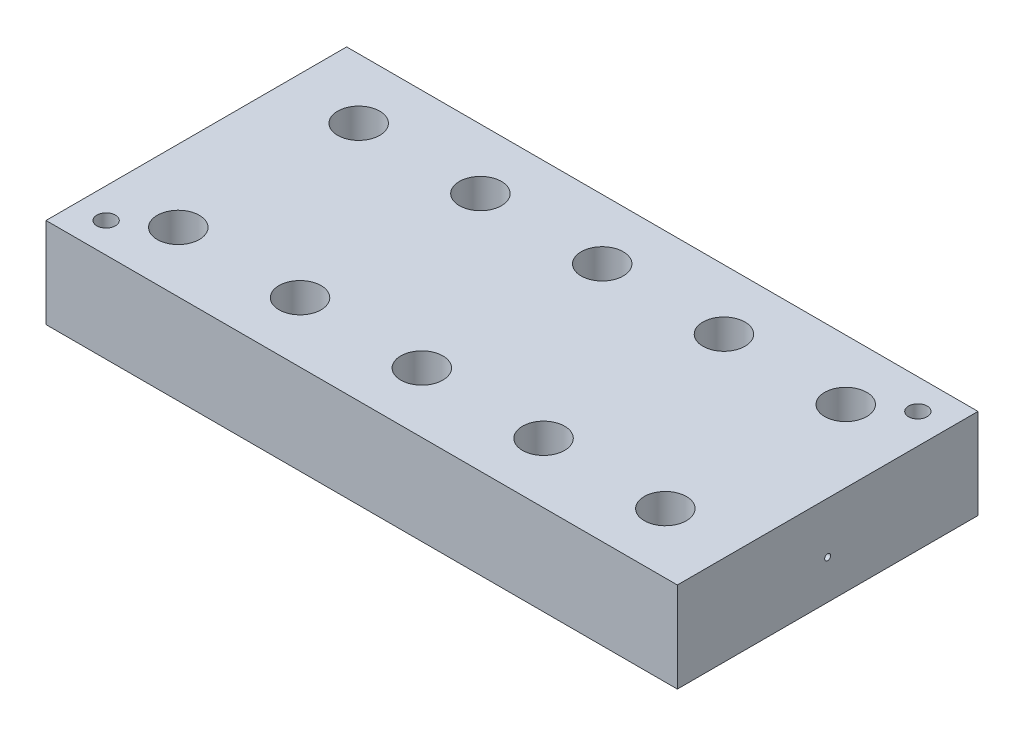
SolidWorks part; units mm, degrees
ref_plane "Front Plane" through (0, 0, 0) normal (0, 0, 1) x (1, 0, 0)
ref_plane "Top Plane" through (0, 0, 0) normal (0, 1, 0) x (1, 0, 0)
ref_plane "Right Plane" through (0, 0, 0) normal (1, 0, 0) x (0, 0, -1)
sketch "Sketch2" plane through (0, 0, 0) normal (0, 1, 0) x (1, 0, 0)
  line L0 (-46.8981, 34.5466) -> (-46.8981, -15.4534)
  line L1 (-46.8981, -15.4534) -> (58.1019, -15.4534)
  line L2 (58.1019, -15.4534) -> (58.1019, 34.5466)
  line L3 (58.1019, 34.5466) -> (-46.8981, 34.5466)
  dimension "D1" = 105
  dimension "D2" = 50
extrude "Boss-Extrude1" add sketch "Sketch2" along normal blind 15
sketch "Sketch3" plane through (0, 0, 0) normal (0, 1, 0) x (1, 0, 0)
  line L0 (74.3548, 9.5466) -> (-56.2815, 9.5466) construction
  line L1 (48.1019, 9.5466) -> (48.1019, 17.0466)
  line L2 (48.1019, 17.0466) -> (-11.8981, 17.0466)
  line L3 (-11.8981, 17.0466) -> (-11.8981, 19.5466)
  line L4 (-11.8981, 19.5466) -> (-36.8981, 19.5466)
  line L5 (-36.8981, 19.5466) -> (-36.8981, 9.5466)
  line L6 (-36.8981, 9.5466) -> (48.1019, 9.5466)
  line L7 (58.1019, -15.4534) -> (58.1019, 34.5466) construction
  line L9 (-46.8981, -15.4534) -> (58.1019, -15.4534) construction
  dimension "D1" = 60
  dimension "D2" = 25
  dimension "D3" = 10
  dimension "D4" = 25
  dimension "D5" = 10
  dimension "D6" = 7.5
sketch "Skizze7" plane through (-46.8981, 0, 0) normal (-1, 0, 0) x (0, 0, 1)
  line L1 (-34.5466, 0) -> (15.4534, 0) construction
  line L3 (-9.5466, -6.0172) -> (-9.5466, 6.0172) construction
  line L4 (15.4534, 15) -> (15.4534, 0) construction
  line L5 (-34.5466, 15) -> (-34.5466, 0) construction
  circle A0 centre (-9.5466, 7.9) radius 2.1
  dimension "D1" = 4.2
  dimension "D2" = 7.9
extrude "Schnitt-Linear austragen6" cut sketch "Skizze7" against normal blind 10
revolve "Schnitt-Rotation1" cut sketch "Sketch3" angle 360 about L0
sketch "Skizze10" plane through (0, 0, 0) normal (0, -1, 0) x (1, 0, 0)
  line L0 (48.1019, -17.0466) -> (-11.8981, -17.0466) construction
  line L1 (38.1019, -17.0466) -> (25.6019, -17.0466)
  line L2 (38.1019, -17.0466) -> (38.1019, -13.0466)
  line L3 (38.1019, -13.0466) -> (25.6019, -13.0466)
  line L4 (25.6019, -17.0466) -> (25.6019, -13.0466)
  line L5 (48.1019, -2.0466) -> (48.1019, -17.0466) construction
  line L10 (85.7448, -9.5466) -> (-66.8579, -9.5466) construction
  line L11 (-46.8981, 15.4534) -> (58.1019, 15.4534) construction
  line L12 (58.1019, -34.5466) -> (-46.8981, -34.5466) construction
  dimension "D1" = 10
  dimension "D2" = 12.5
  dimension "D5" = 4
revolve "Rotation3" add sketch "Skizze10" angle 180 about L10 reverse direction yes
sketch "Skizze11" plane through (0, 0, 0) normal (0, -1, 0) x (1, 0, 0)
  line L0 (25.6019, -17.0466) -> (-11.8981, -17.0466) construction
  line L1 (13.1019, -17.0466) -> (0.6019, -17.0466)
  line L2 (13.1019, -17.0466) -> (13.1019, -13.0466)
  line L3 (13.1019, -13.0466) -> (0.6019, -13.0466)
  line L4 (0.6019, -17.0466) -> (0.6019, -13.0466)
  line L5 (38.1019, -13.0466) -> (25.6019, -13.0466) construction
  line L6 (25.6019, -13.0466) -> (25.6019, -17.0466) construction
  line L7 (95.0378, -9.5466) -> (-94.5432, -9.5466) construction
  line L8 (-46.8981, 15.4534) -> (58.1019, 15.4534) construction
  line L9 (58.1019, -34.5466) -> (-46.8981, -34.5466) construction
  point P10 (25.6019, -15.0466)
  dimension "D1" = 12.5
  dimension "D2" = 12.5
revolve "Rotation4" add sketch "Skizze11" angle 180 about L7 reverse direction yes
ref_plane "Ebene6" through (0, 0, -9.5466) normal (0, 0, 1) x (1, 0, 0)
sketch "Skizze13" plane through (-46.8981, 0, 0) normal (-1, 0, 0) x (0, 0, 1)
  line L0 (-34.5466, 0) -> (15.4534, 0) construction
  line L1 (15.4534, 15) -> (0.4534, 15)
  line L2 (15.4534, 15) -> (15.4534, 5)
  line L3 (15.4534, 5) -> (0.4534, 5)
  line L4 (0.4534, 15) -> (0.4534, 5)
  line L5 (-34.5466, 0) -> (15.4534, 0) construction
  line L6 (-34.5466, 15) -> (-19.5466, 15)
  line L7 (-34.5466, 15) -> (-34.5466, 5)
  line L8 (-34.5466, 5) -> (-19.5466, 5)
  line L9 (-19.5466, 15) -> (-19.5466, 5)
  dimension "D1" = 15
  dimension "D2" = 5
  dimension "D3" = 15
  dimension "D4" = 5
ref_plane "Plane1" through (58.1019, 0, 0) normal (1, 0, 0) x (0, 0, -1)
sketch "Sketch5" plane through (58.1019, 0, 0) normal (1, 0, 0) x (0, 0, -1)
  line L3 (-15.4534, 15) -> (-15.4534, 0) construction
  line L5 (-15.4534, 0) -> (34.5466, 0) construction
  circle A0 centre (9.5466, 6.5) radius 0.5
  dimension "D1" = 1
  dimension "D2" = 25
  dimension "D3" = 6.5
extrude "Cut-Extrude2" cut sketch "Sketch5" against normal up to next
sketch "Skizze14" plane through (-36.8981, 0, 0) normal (1, 0, 0) x (0, 0, -1)
  line L0 (19.5466, 0) -> (-0.4534, 0) construction
  circle A0 centre (9.5466, 0) radius 5.5
  dimension "D1" = 11
sketch "Skizze15" plane through (48.1019, 0, 0) normal (-1, 0, 0) x (0, 0, 1)
  line L0 (-2.0466, 0) -> (-17.0466, 0) construction
  circle A0 centre (-9.5466, 0) radius 4
  dimension "D1" = 8
loft "Schnitt-Ausformung1" cut profiles "Skizze14", "Skizze15" connector at (-36.8981, -5.2276, -7.8372) connector at (48.1019, -3.7635, -8.1917)
fillet "Verrundung1" radius 1 10 edges at (38.1019, 4.1765, -9.5466) (25.6019, 4.3971, -9.5466) (13.1019, 4.6176, -9.5466) (0.6019, 4.8382, -9.5466) (38.1019, 7.5, -9.5466) (13.1019, 7.5, -9.5466) (25.6019, 7.5, -9.5466) (-11.8981, 10, -9.5466) (-11.8981, 7.5, -9.5466) (0.6019, 7.5, -9.5466)
sketch "Skizze20" plane through (0, 0, 0) normal (0, -1, 0) x (1, 0, 0)
  line L0 (58.1019, -34.5466) -> (-46.8981, -34.5466) construction
  line L1 (58.1019, 15.4534) -> (58.1019, -34.5466) construction
  line L2 (-46.8981, -34.5466) -> (-46.8981, 15.4534) construction
  line L3 (-46.8981, 15.4534) -> (58.1019, 15.4534) construction
  circle A0 centre (53.1019, -29.5466) radius 1.55
  circle A1 centre (-41.8981, 10.4534) radius 1.55
  dimension "D1" = 3.1
  dimension "D2" = 5
  dimension "D3" = 5
  dimension "D4" = 5
  dimension "D5" = 5
extrude "Ausrichtungsstifte" cut sketch "Skizze20" against normal through all and the other way through all
hole_wizard "Stirnsenkung für M3 Flachkopfschraube mit Schlitz2" positions "Skizze21" profile "Skizze22" counterbore size "M3" standard "DIN" end condition through all
sketch "Skizze21" plane through (0, 15, 0) normal (0, 1, 0) x (1, 0, 0)
  line L0 (58.1019, 34.5466) -> (-46.8981, 34.5466) construction
  line L1 (58.1019, -15.4534) -> (58.1019, 34.5466) construction
  point P63 (46.1019, 24.5466)
  point P77 (25.8519, 24.5466)
  point P78 (5.6019, 24.5466)
  point P79 (-14.6481, 24.5466)
  point P80 (-34.8981, 24.5466)
  point P81 (25.8519, -5.4534)
  point P82 (5.6019, -5.4534)
  point P83 (-14.6481, -5.4534)
  point P84 (-34.8981, -5.4534)
  point P85 (46.1019, -5.4534)
  dimension "D1" = 10
  dimension "D2" = 12
  dimension "D3" = 5
  dimension "D4" = 2
sketch "Skizze22" plane through (46.1019, 15, -24.5466) normal (1, 0, 0) x (0, 0, 1)
  line L0 (0, 0) -> (0, 15)
  line L1 (0, 15) -> (1.7, 15)
  line L3 (1.7, 15) -> (1.7, 9.9)
  line L4 (1.7, 9.9) -> (3.5, 9.9)
  line L5 (3.5, 9.9) -> (3.5, 0)
  line L7 (3.5, 0) -> (0, 0)
  line L11 (0, -6.35) -> (0, 107.95) construction
  dimension "Bohrerdurchmesser" = 3.4
  dimension "Bohrungstiefe" = 15
  dimension "Senkdurchmesser2" = 7
  dimension "Senktiefe2" = 9.9
